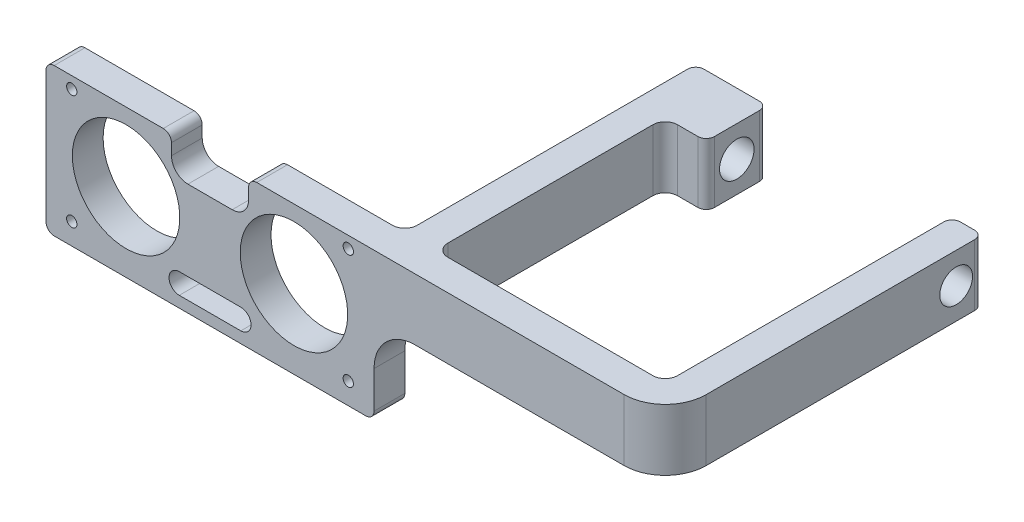
SolidWorks part; units mm, degrees
ref_plane "Front Plane" through (0, 0, 0) normal (0, 0, 1) x (1, 0, 0)
ref_plane "Top Plane" through (0, 0, 0) normal (0, 1, 0) x (1, 0, 0)
ref_plane "Right Plane" through (0, 0, 0) normal (1, 0, 0) x (0, 0, -1)
sketch "Sketch10" plane through (0, 0, 0) normal (0, 0, 1) x (1, 0, 0)
  line L0 (-21.41, 17.74) -> (-21.41, 0) construction
  line L1 (-21.41, 0) -> (21.41, 0) construction
  line L2 (21.41, 0) -> (21.41, 17.74) construction
  line L3 (21.41, 17.74) -> (-21.41, 17.74) construction
  line L4 (0, 0) -> (0, -3.312) construction
  line L5 (-13, 8.87) -> (13, 8.87) construction
  line L6 (13, 8.87) -> (21.41, 8.87) construction
  line L7 (0, 13.9911) -> (0, 0) construction
  line L8 (-4.7625, 0) -> (4.7625, 0) construction
  line L9 (-4.7625, 1.5875) -> (4.7625, 1.5875)
  line L10 (-4.7625, -1.5875) -> (4.7625, -1.5875)
  line L16 (5.969, 19.548) -> (5.969, 16.5311)
  line L17 (3.429, 13.9911) -> (-3.429, 13.9911)
  line L18 (-5.969, 16.5311) -> (-5.969, 19.548)
  line L19 (-5.969, 19.548) -> (-25.4, 19.548)
  line L20 (-25.4, 19.548) -> (-25.4, -3.312)
  line L21 (-25.4, -3.312) -> (25.4, -3.312)
  line L22 (25.4, -3.312) -> (25.4, 19.548)
  line L23 (25.4, 19.548) -> (5.969, 19.548)
  arc A0 (-4.7625, 1.5875) -> (-4.7625, -1.5875) centre (-4.7625, 0) ccw
  arc A1 (4.7625, -1.5875) -> (4.7625, 1.5875) centre (4.7625, 0) ccw
  arc A4 (3.429, 13.9911) -> (5.969, 16.5311) centre (3.429, 16.5311) ccw
  arc A5 (-5.969, 16.5311) -> (-3.429, 13.9911) centre (-3.429, 16.5311) ccw
  circle A8 centre (21.41, 17.74) radius 0.8
  circle A9 centre (21.41, 0) radius 0.8
  circle A10 centre (-21.41, 17.74) radius 0.8
  circle A11 centre (-21.41, 0) radius 0.8
  circle A12 centre (13, 8.87) radius 8.3185
  circle A13 centre (-13, 8.87) radius 8.3185
  point P31 (0, 0)
  dimension "D1" = 16.637
  dimension "D2" = 1.6
  dimension "D3" = 2.54
  dimension "D12" = 8.41
  dimension "D13" = 9.525
  dimension "D4" = 3.0169
  dimension "D5" = 6.858
  dimension "D6" = 1.808
  dimension "D7" = 17.74
  dimension "D8" = 42.82
  dimension "D9" = 50.8
  dimension "D10" = 22.86
  dimension "D11" = 26
  dimension "D14" = 3.175
extrude "Boss-Extrude1" add sketch "Sketch10" along normal blind 4.7625
sketch "Sketch11" plane through (0, 19.548, 0) normal (0, 1, 0) x (1, 0, 0)
  line L0 (25.4, -4.7625) -> (70.485, -4.7625)
  line L1 (70.485, -4.7625) -> (70.485, 44.4246)
  line L2 (70.485, 44.4246) -> (65.7225, 44.4246)
  line L3 (65.7225, 44.4246) -> (65.7225, 0)
  line L4 (65.7225, 0) -> (30.1625, 0)
  line L5 (25.4, -4.7625) -> (25.4, 0) construction
  line L6 (25.4, -4.7625) -> (25.4, 45.0596)
  line L9 (30.1625, 35.56) -> (30.1625, 0)
  line L10 (30.1625, 0) -> (25.4, 0) construction
  line L11 (36.5125, 35.56) -> (36.5125, 45.0596)
  line L13 (30.1625, 35.56) -> (36.5125, 35.56)
  line L14 (25.4, 45.0596) -> (36.5125, 45.0596)
  dimension "D1" = 35.56
  dimension "D2" = 9.4996
  dimension "D3" = 6.35
  dimension "D4" = 35.56
extrude "Boss-Extrude2" add sketch "Sketch11" against normal blind 9.525 contours L14 L11 L13 L9 L4 L3 L2 L1 L0 L6
fillet "Fillet1" radius 1.905 4 edges at (30.1625, 14.7855, -35.56) (30.1625, 14.7855, 0) (65.7225, 14.7855, 0) (25.4, 14.7855, 0)
fillet "Fillet2" radius 6.35 2 edges at (25.4, 10.023, 2.3813) (70.485, 14.7855, 4.7625)
sketch "Sketch13" plane through (25.4, 0, 0) normal (-1, 0, 0) x (0, 0, 1)
  line L0 (-40.2971, 14.7855) -> (-45.0596, 14.7855) construction
  line L1 (-45.0596, 10.023) -> (-45.0596, 19.548) construction
  line L2 (-40.2971, 14.7855) -> (-40.2971, 19.548) construction
  line L3 (-1.905, 19.548) -> (-45.0596, 19.548) construction
  circle A0 centre (-40.2971, 14.7855) radius 2.675
  dimension "D1" = 5.35
extrude "Cut-Extrude1" cut sketch "Sketch13" against normal up to next contours A0
sketch "Sketch14" plane through (65.7225, 0, 0) normal (-1, 0, 0) x (0, 0, 1)
  circle A0 centre (-40.2971, 14.7855) radius 2.54
  circle A1 centre (-40.2971, 14.7855) radius 2.675 construction
  dimension "D1" = 5.08
extrude "Cut-Extrude2" cut sketch "Sketch14" against normal through all
fillet "Fillet3" radius 1.27 11 edges at (-25.4, -3.312, 2.3813) (25.4, -3.312, 2.3813) (-25.4, 19.548, 2.3813) (-5.969, 19.548, 2.3813) (5.969, 19.548, 2.3813) (36.5125, 14.7855, -35.56) (36.5125, 14.7855, -45.0596) (70.485, 14.7855, -44.4246) (65.7225, 14.7855, -44.4246) (25.4, 14.7855, -45.0596) (27.6225, 10.023, 0)
chamfer "Chamfer1" distance 1.27 angle 45 1 edges at (25.4, 12.1105, -40.2971)
